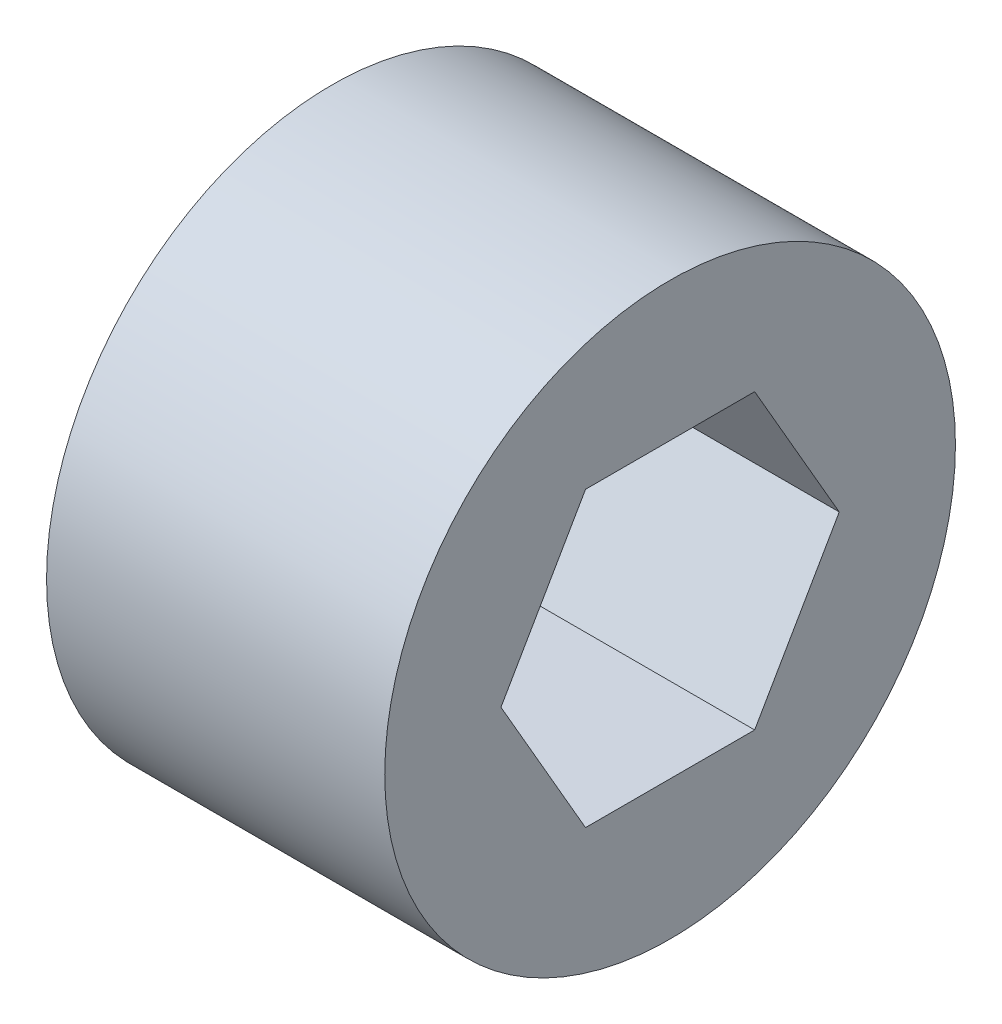
SolidWorks part; units mm, degrees
material "PET"
ref_plane "Front" through (0, 0, 0) normal (0, 0, 1) x (1, 0, 0)
ref_plane "Top" through (0, 0, 0) normal (0, 1, 0) x (1, 0, 0)
ref_plane "Right" through (0, 0, 0) normal (1, 0, 0) x (0, 0, -1)
sketch "Sketch1" plane through (0, 0, 0) normal (1, 0, 0) x (0, 0, -1)
  line L1 (5.6459, 0) -> (2.823, 4.8895)
  line L2 (2.823, 4.8895) -> (-2.823, 4.8895)
  line L3 (-2.823, 4.8895) -> (-5.6459, 0)
  line L4 (-5.6459, 0) -> (-2.823, -4.8895)
  line L5 (-2.823, -4.8895) -> (2.823, -4.8895)
  line L6 (2.823, -4.8895) -> (5.6459, 0)
  circle A0 centre (0, 0) radius 4.8895 construction
  circle A1 centre (0, 0) radius 9.525
  dimension "D2" = 19.05
  dimension "D1" = 9.779
extrude "Boss-Extrude1" add sketch "Sketch1" along normal blind 11.2889
